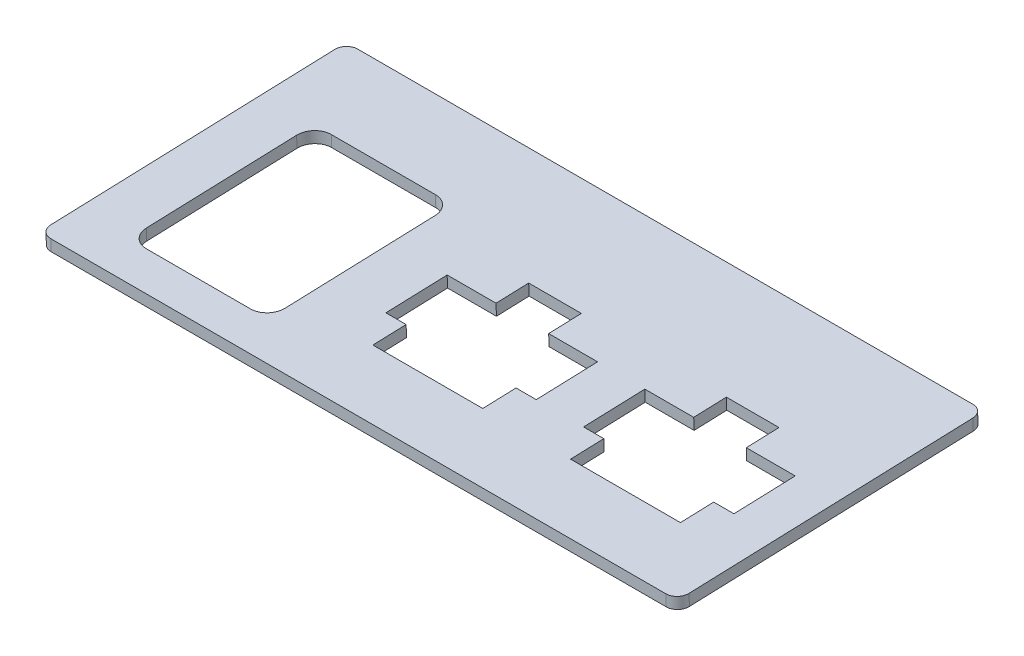
SolidWorks part; units mm, degrees
ref_plane "Front Plane" through (0, 0, 0) normal (0, 0, 1) x (1, 0, 0)
ref_plane "Top Plane" through (0, 0, 0) normal (0, 1, 0) x (1, 0, 0)
ref_plane "Right Plane" through (0, 0, 0) normal (1, 0, 0) x (0, 0, -1)
sketch "Sketch1" plane through (0, -68.9908, -2.4092) normal (0, 0.9994, 0.0349) x (1, 0, 0)
  line L1 (-53.6759, -2.8069) -> (-56.175, -2.8069) construction
  line L2 (55.275, 48.7944) -> (-55.275, 48.7944) construction
  line L8 (-55.175, -4.3069) -> (55.175, -4.3069)
  line L9 (55.175, -4.3069) -> (55.175, 48.7944)
  line L10 (55.175, 48.7944) -> (-55.175, 48.7944)
  line L11 (-55.175, 48.7944) -> (-55.175, -4.3069)
  dimension "D1" = 1.5
  dimension "D2" = 3.0034
  dimension "D3" = 3.0034
extrude "Boss-Extrude1" add sketch "Sketch1" along normal blind 2
sketch "Sketch2" plane through (0, -68.9908, -2.4092) normal (0, -0.9994, -0.0349) x (1, 0, 0)
  line L0 (-4.05, -23.5688) -> (-4.05, -29.2188)
  line L1 (-43.175, -2.2188) -> (-25.175, -2.2188)
  line L2 (-46.175, -5.2188) -> (-46.175, -31.2188)
  line L3 (-43.175, -34.2188) -> (-25.175, -34.2188)
  line L4 (-22.175, -5.2188) -> (-22.175, -31.2188)
  line L5 (-12.5, -12.9688) -> (-9, -12.9688)
  line L6 (-12.5, -12.9688) -> (-12.5, -23.5688)
  line L7 (-12.5, -23.5688) -> (-4.05, -23.5688)
  line L8 (13.5, -12.9688) -> (13.5, -23.5688)
  line L9 (-9, -7.2188) -> (10, -7.2188)
  line L10 (-9, -7.2188) -> (-9, -12.9688)
  line L11 (-4.05, -29.2188) -> (5.05, -29.2188)
  line L12 (10, -7.2188) -> (10, -12.9688)
  line L13 (10, -12.9688) -> (13.5, -12.9688)
  line L14 (5.05, -23.5688) -> (5.05, -29.2188)
  line L15 (5.05, -23.5688) -> (13.5, -23.5688)
  line L16 (-13, -4.7188) -> (14, -31.7188) construction
  line L17 (-13, -4.7188) -> (14, -4.7188) construction
  line L18 (-13, -4.7188) -> (-13, -31.7188) construction
  line L19 (-13, -31.7188) -> (14, -31.7188) construction
  line L20 (14, -4.7188) -> (14, -31.7188) construction
  line L21 (17.5875, 3.7502) -> (17.5875, -36.664) construction
  line L22 (47.675, -18.2688) -> (21.675, -18.2688) construction
  line L23 (34.675, -7.2188) -> (34.675, -29.2188) construction
  line L24 (21.175, -4.7188) -> (21.175, -31.7188) construction
  line L25 (48.175, -31.7188) -> (21.175, -31.7188) construction
  line L26 (48.175, -4.7188) -> (48.175, -31.7188) construction
  line L27 (48.175, -4.7188) -> (21.175, -4.7188) construction
  line L28 (-48.175, -18.2188) -> (-46.175, -18.2188) construction
  line L29 (-48.175, -0.2188) -> (-20.175, -0.2188) construction
  line L30 (-48.175, -0.2188) -> (-48.175, -36.2188) construction
  line L31 (-48.175, -36.2188) -> (-20.175, -36.2188) construction
  line L32 (-20.175, -0.2188) -> (-20.175, -36.2188) construction
  line L33 (-34.175, -2.2188) -> (-34.175, -0.2188) construction
  line L34 (0.5, -7.2188) -> (0.5, -29.2188) construction
  line L35 (-12.5, -18.2688) -> (13.5, -18.2688) construction
  line L36 (48.175, -4.7188) -> (21.175, -31.7188) construction
  line L37 (30.125, -23.5688) -> (21.675, -23.5688)
  line L38 (30.125, -23.5688) -> (30.125, -29.2188)
  line L39 (25.175, -12.9688) -> (21.675, -12.9688)
  line L40 (25.175, -7.2188) -> (25.175, -12.9688)
  line L41 (39.225, -29.2188) -> (30.125, -29.2188)
  line L42 (44.175, -7.2188) -> (44.175, -12.9688)
  line L43 (44.175, -7.2188) -> (25.175, -7.2188)
  line L44 (21.675, -12.9688) -> (21.675, -23.5688)
  line L45 (47.675, -23.5688) -> (39.225, -23.5688)
  line L46 (47.675, -12.9688) -> (47.675, -23.5688)
  line L47 (47.675, -12.9688) -> (44.175, -12.9688)
  line L48 (39.225, -23.5688) -> (39.225, -29.2188)
  line L49 (21.175, -18.2188) -> (14, -18.2188) construction
  line L50 (-55.175, 4.3069) -> (55.175, 4.3069) construction
  line L51 (48.175, -18.2188) -> (52.175, -18.2188) construction
  line L52 (55.175, 4.3069) -> (55.175, -48.7944) construction
  line L53 (-46.7914, -40.7445) -> (46.7914, -40.7445) construction
  line L54 (-13, -18.2188) -> (-20.175, -18.2188) construction
  line L55 (-34.175, -0.2188) -> (-34.175, 4.3069) construction
  line L56 (-34.175, -36.2188) -> (-34.175, -40.7445) construction
  line L57 (-55.175, -48.7944) -> (-55.175, 4.3069) construction
  line L58 (-48.175, -18.2188) -> (-52.175, -18.2188) construction
  arc A0 (-46.175, -31.2188) -> (-43.175, -34.2188) centre (-43.175, -31.2188) ccw
  arc A1 (-25.175, -34.2188) -> (-22.175, -31.2188) centre (-25.175, -31.2188) ccw
  arc A2 (-25.175, -2.2188) -> (-22.175, -5.2188) centre (-25.175, -5.2188) cw
  arc A3 (-43.175, -2.2188) -> (-46.175, -5.2188) centre (-43.175, -5.2188) ccw
  point P28 (0.5, -18.2188)
  point P63 (34.675, -18.2188)
  dimension "D1" = 3
  dimension "D2" = 32
  dimension "D3" = 24
  dimension "D4" = 28
  dimension "D5" = 36
  dimension "D6" = 26
  dimension "D7" = 22
  dimension "D8" = 10.6
  dimension "D9" = 19
  dimension "D10" = 9.1
  dimension "D11" = 5.75
  dimension "D12" = 27
  dimension "D13" = 27
  dimension "D14" = 4
  dimension "D15" = 3
  dimension "D16" = 3
extrude "Cut-Extrude1" cut sketch "Sketch2" against normal up to next
fillet "Fillet1" radius 2 4 edges at (-55.175, -68.1418, 1.93) (55.175, -68.1418, 1.93) (55.175, -66.2886, -51.139) (-55.175, -66.2886, -51.139)
